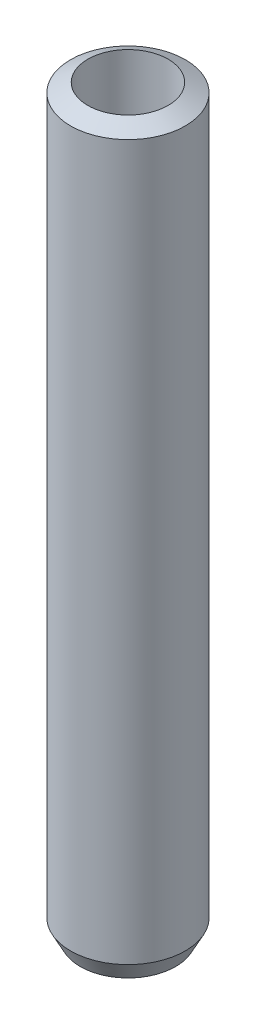
SolidWorks part; units mm, degrees
ref_plane "Front Plane" through (0, 0, 0) normal (0, 0, 1) x (1, 0, 0)
ref_plane "Top Plane" through (0, 0, 0) normal (0, 1, 0) x (1, 0, 0)
ref_plane "Right Plane" through (0, 0, 0) normal (1, 0, 0) x (0, 0, -1)
sketch "Sketch1" plane through (0, 0, 0) normal (0, 1, 0) x (1, 0, 0)
  circle A0 centre (0, 0) radius 20
  dimension "SHAFT_OD" = 40
extrude "Boss-Extrude1" add sketch "Sketch1" along normal blind 258.7697
sketch "Sketch2" plane through (0, 0, 0) normal (0, 1, 0) x (1, 0, 0)
  circle A0 centre (0, 0) radius 13.9872
  dimension "BORE_D" = 27.9743
extrude "Cut-Extrude1" cut sketch "Sketch2" along normal through all
chamfer "Chamfer1" distance 3.3724 angle 62.303 2 edges at (0, 258.7697, 20) (0, 0, 20) first distance on face at (0, 258.7697, 20) first distance on face at (0, 0, 13.9872)
